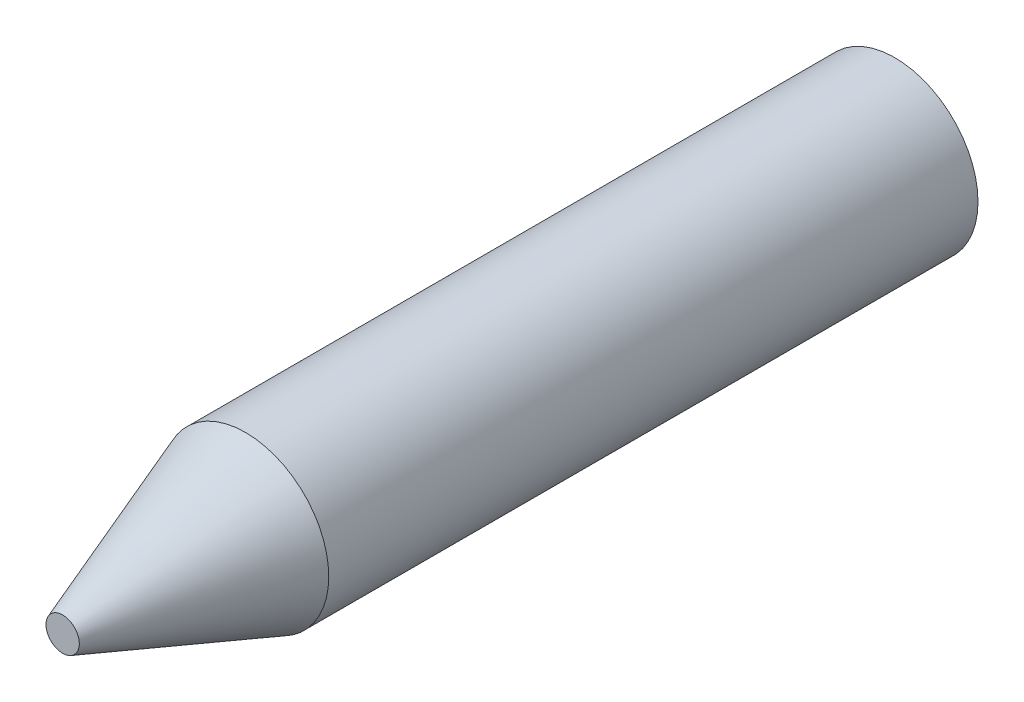
SolidWorks part; units mm, degrees
ref_plane "Front Plane" through (0, 0, 0) normal (0, 0, 1) x (1, 0, 0)
ref_plane "Top Plane" through (0, 0, 0) normal (0, 1, 0) x (1, 0, 0)
ref_plane "Right Plane" through (0, 0, 0) normal (1, 0, 0) x (0, 0, -1)
sketch "Sketch1" plane through (0, 0, 0) normal (0, 1, 0) x (1, 0, 0)
  line L0 (0, -68.6932) -> (0, 107.7398) construction
  line L1 (0, 100) -> (10, 100)
  line L2 (10, 100) -> (10, 21.9798)
  line L4 (0, 0) -> (0, 100)
  line L5 (10, 21.9798) -> (2, 0)
  line L6 (2, 0) -> (0, 0)
  point P8 (10, 83.4948)
  point P9 (6.0037, 100)
  point P10 (10, -121.9798)
  point P11 (2, 0)
  dimension "D1" = 10
  dimension "D2" = 100
  dimension "D3" = 20
  dimension "D4" = 2
revolve "Revolve1" add sketch "Sketch1" angle 360 about L0
